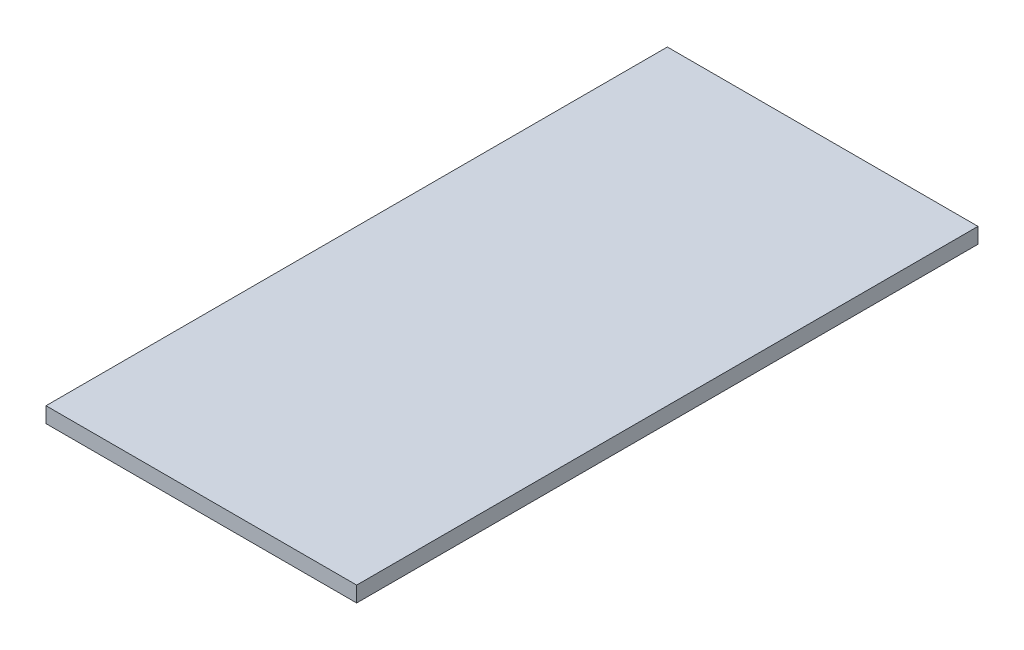
SolidWorks part; units mm, degrees
material "6061 Alloy"
ref_plane "Front Plane" through (0, 0, 0) normal (0, 0, 1) x (1, 0, 0)
ref_plane "Top Plane" through (0, 0, 0) normal (0, 1, 0) x (1, 0, 0)
ref_plane "Right Plane" through (0, 0, 0) normal (1, 0, 0) x (0, 0, -1)
sketch "Sketch1" plane through (0, 0, 0) normal (0, 1, 0) x (1, 0, 0)
  line L1 (-50, -100) -> (50, -100)
  line L2 (-50, -100) -> (-50, 100)
  line L3 (-50, 100) -> (50, 100)
  line L4 (50, -100) -> (50, 100)
  line L5 (-50, -100) -> (50, 100) construction
  line L6 (-50, 100) -> (50, -100) construction
  point P0 (0, 0)
  dimension "D1" = 100
  dimension "D2" = 200
extrude "Boss-Extrude1" add sketch "Sketch1" along normal blind 5
